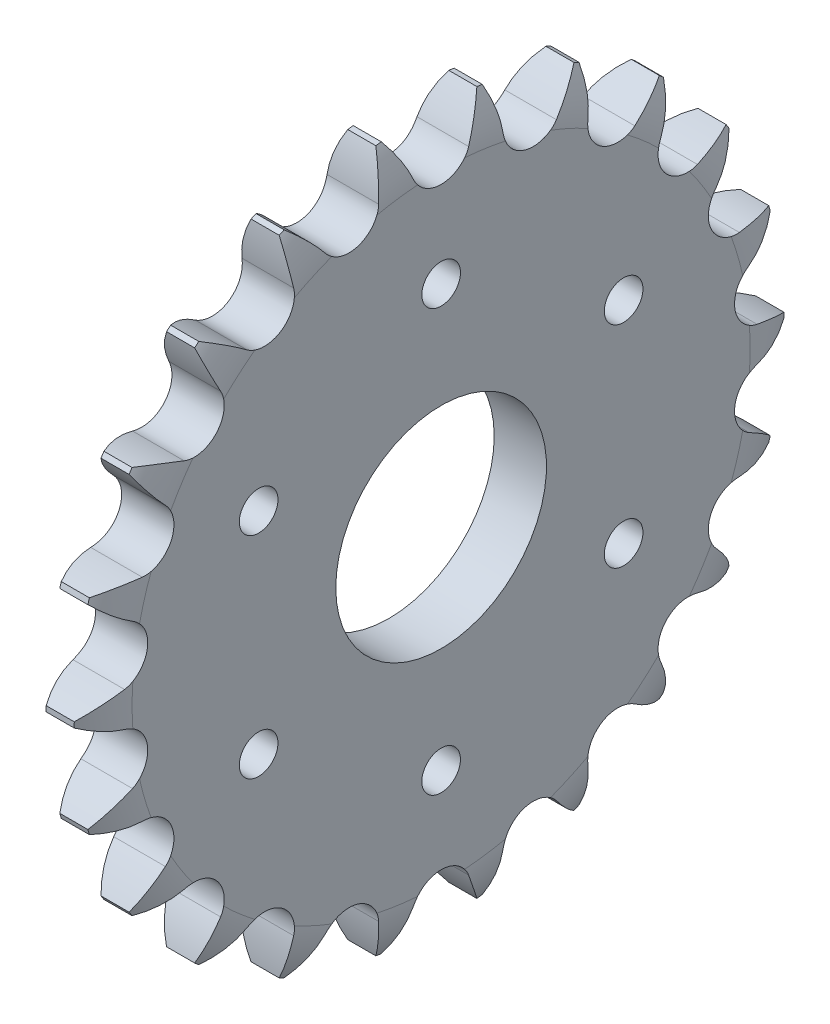
SolidWorks part; units mm, degrees
ref_plane "Plane1" through (0, 0, 0) normal (0, 0, 1) x (1, 0, 0)
ref_plane "Plane2" through (0, 0, 0) normal (0, 1, 0) x (1, 0, 0)
ref_plane "Plane3" through (0, 0, 0) normal (1, 0, 0) x (0, 0, -1)
sketch "Clipboard" plane through (0, 0, 0) normal (0, 1, 0) x (1, 0, 0)
  line L0 (0, 0) -> (14.719, -5.9469)
  line L1 (-15, 0) -> (100, 0) construction
  line L2 (0, 0) -> (-1.3675, 1.5456)
  line L3 (0, 0) -> (-14.8288, 5.6677)
  line L4 (0, 0) -> (2.8743, 1.1613)
  line L5 (0, 0) -> (-46.8476, -17.4728)
  line L6 (0, 0) -> (-7.4026, -4.9946)
  line L7 (-1.3675, 1.5456) -> (44.6582, 21.0824)
  line L8 (-76.2, 38.1) -> (-72.9, 38.1)
  line L9 (-73.5462, 42.5082) -> (-72.9534, 42.6013)
  line L10 (-74, 16.6356) -> (-55.89, 16.6356)
  circle A0 centre (0, 0) radius 5.08
  circle A1 centre (0, 0) radius 37.5
  circle A2 centre (0, 0) radius 37.5
  dimension "Num_teeth" = 22
  dimension "Thickness" = 8.93
sketch "BasProSke" plane through (0, 0, 0) normal (0, 1, 0) x (1, 0, 0)
  line L0 (-10, 0) -> (60, 0) construction
  line L1 (0, 0) -> (0, 52.7889)
  line L2 (0, 0) -> (8.93, 0)
  line L3 (8.93, 0) -> (8.93, 52.7889)
  line L4 (6.8663, 60.6161) -> (2.0638, 60.6161)
  arc A0 (0, 52.7889) -> (2.0638, 60.6161) centre (15.875, 52.7889) cw
  arc A1 (8.93, 52.7889) -> (6.8663, 60.6161) centre (-6.945, 52.7889) ccw
  dimension "D1" = 15.875
  dimension "Thickness" = 8.93
  dimension "Diameter" = 121.2322
revolve "Base-Revolve" add sketch "BasProSke" angle 360 about L0
sketch "TooCutSke" plane through (0, 0, 0) normal (1, 0, 0) x (0, 0, -1)
  line L0 (0, 55.825) -> (4.7557, 53.8992) construction
  line L1 (0, 0) -> (0, 107) construction
  line L2 (0, 55.825) -> (-10, 55.825) construction
  line L3 (0, 55.825) -> (-4.7557, 53.8992) construction
  arc A0 (4.7557, 53.8992) -> (8.5049, 60.5214) centre (31.8771, 42.9164) cw
  arc A1 (4.7557, 53.8992) -> (-4.7557, 53.8992) centre (0, 55.825) cw
  arc A2 (-4.7557, 53.8992) -> (-8.5049, 60.5214) centre (-31.8771, 42.9164) ccw
  arc A3 (8.5049, 60.5214) -> (-8.5049, 60.5214) centre (0, 0) ccw
extrude "ToothCut" cut sketch "TooCutSke" along normal through all
pattern_circular "TeethCuts" count 22 every 16.364 about axis through (-10, 0, 0) along (1, 0, 0) of "ToothCut"
sketch "HubNeaOneSke" plane through (0, 0, 0) normal (-1, 0, 0) x (0, 0, 1)
  circle A0 centre (0, 0) radius 37.5
  dimension "Diameter" = 75
extrude "HubNearOne" [suppressed] add sketch "HubNeaOneSke" along normal blind 41.0705
fillet "HubNearOneFillet" [suppressed] radius 0.6
sketch "HubNeaBotSke" plane through (0, 0, 0) normal (-1, 0, 0) x (0, 0, 1)
  circle A0 centre (0, 0) radius 37.5
  dimension "Diameter" = 75
extrude "HubNearBoth" [suppressed] add sketch "HubNeaBotSke" along normal blind 20.5353
fillet "HubNearBothFillet" [suppressed] radius 0.6
ref_plane "FarPln" through (8.93, 0, 0) normal (1, 0, 0) x (0, 0, -1)
sketch "HubFarSke" plane through (8.93, 0, 0) normal (1, 0, 0) x (0, 0, -1)
  circle A0 centre (0, 0) radius 37.5
  dimension "Diameter" = 75
extrude "HubFar" [suppressed] add sketch "HubFarSke" along normal blind 20.5353
fillet "HubFarFillet" [suppressed] radius 0.6
sketch "BorSke" plane through (0, 0, 0) normal (1, 0, 0) x (0, 0, -1)
  circle A0 centre (0, 0) radius 18
  dimension "Diameter" = 36
extrude "Bore" cut sketch "BorSke" along normal mid plane 100.001
sketch "KeySke" plane through (0, 0, 0) normal (1, 0, 0) x (0, 0, -1)
  line L0 (-5, 0) -> (-5, 21.3)
  line L1 (-5, 21.3) -> (5, 21.3)
  line L2 (5, 21.3) -> (5, 0)
  line L3 (0, 0) -> (0, 34) construction
  line L4 (-5, 0) -> (5, 0)
  dimension "Width" = 10
extrude "Keyway" [suppressed] cut sketch "KeySke" along normal mid plane 100.001
pattern_circular "Keyway2" [suppressed] count 2 every 90 about axis through (-10, 0, 0) along (1, 0, 0) reverse direction yes
ref_axis "Assi1" through (8.93, 0, 0) along (-1, 0, 0)
hole_wizard "Foro per Vite M6-1" positions "Schizzo2" profile "Schizzo3" hole size "M6" standard "ISO"
sketch "Schizzo2" plane through (8.93, 0, 0) normal (1, 0, 0) x (0, 0, -1)
  point P0 (0, 36)
  dimension "D1" = 36
sketch "Schizzo3" plane through (8.93, 36, 0) normal (0, 1, 0) x (0, 0, -1)
  line L0 (0, 0) -> (0, 12)
  line L1 (0, 12) -> (3.3, 10.0172)
  line L2 (3.3, 10.0172) -> (3.3, 0)
  line L5 (3.3, 0) -> (0, 0)
  line L10 (0, 12) -> (-3.3, 10.0172) construction
  line L11 (0, -6.35) -> (0, 107.95) construction
  dimension "Hole Dia." = 6.6
  dimension "Hole Depth" = 12
  dimension "Drill Angle" = 118
pattern_circular "RipetizioneCircolare1" count 6 over 360 about axis through (8.93, 0, 0) along (1, 0, 0) of "Foro per Vite M6-1"
ref_plane "Piano1" through (4.465, 0, 0) normal (1, 0, 0) x (0, 0, -1)
sketch "Schizzo4" plane through (4.465, 0, 0) normal (1, 0, 0) x (0, 0, -1)
  circle A0 centre (0, 0) radius 55.83
  dimension "D1" = 111.66
equation "' \"Pitch@Clipboard\" = 12.7"
equation "' \"Num_strands@Clipboard\" = 1"
equation "' \"Num_teeth@Clipboard\" = 9"
equation "' \"Hub_dia@Clipboard\" = 50"
equation "' \"Overall_len@Clipboard\" = 3"
equation "' \"Diameter@BorSke\" = 12"
equation "' \"T_dim@Clipboard\" = 1"
equation "' \"Width@KeySke\" = 2"
equation "' \"Dr@Clipboard\" = 8.51"
equation "' \"Face_width@Clipboard\" = 7.2"
equation "' \"Side_radius@Clipboard\" = 12.7"
equation "' \"Side_relief@Clipboard\" = 1.27"
equation "' \"Transv_pitch@Clipboard\" = 13.92"
equation "' \"Show_teeth@Clipboard\" = 9"
equation "' \"Fillet_rad@Clipboard\" = 0.6"
equation "' \"Plate_wid@Clipboard\" = 11.8"
equation "\"Num_teeth@Clipboard\" = int( \"Num_teeth@Clipboard\" )"
equation "\"Num_teeth@Clipboard\" = ((sgn( \"Num_teeth@Clipboard\" - 5.0)+1)*( \"Num_teeth@Clipboard\" - 5.0))/2 +5.0"
equation "\"Num_teeth@Clipboard\" = ((sgn( \"Num_teeth@Clipboard\" - 200.0)-1)*( \"Num_teeth@Clipboard\" - 200.0))/-2 +200.0"
equation "\"MHD@Clipboard\" = \"Pitch@Clipboard\" * (1.0 / tan(3.14159265 / \"Num_teeth@Clipboard\" )) - 1.04 * \"Plate_wid@Clipboard\" - 0.76"
equation "\"Thickness@Clipboard\"  = \"Face_width@Clipboard\" + (\"Num_strands@Clipboard\" - 1) * \"Transv_pitch@Clipboard\""
equation "\"OAL@Clipboard\" = \"Thickness@Clipboard\" + 2 * \"Fillet_rad@Clipboard\" + 1"
equation "\"MHD@Clipboard\" = ((sgn( \"MHD@Clipboard\" - \"Hub_dia@Clipboard\" )-1)*( \"MHD@Clipboard\" - \"Hub_dia@Clipboard\" ))/-2+ \"Hub_dia@Clipboard\""
equation "\"OAL@Clipboard\" = ((sgn( \"OAL@Clipboard\" - \"Overall_len@Clipboard\" )+1)*( \"OAL@Clipboard\" - \"Overall_len@Clipboard\" ))/2 + \"Overall_len@Clipboard\" + 0.0005"
equation "\"Num_teeth@TeethCuts\" = int( \"Show_teeth@Clipboard\" ) + 1"
equation "\"Num_teeth@TeethCuts\" = ((sgn( \"Num_teeth@TeethCuts\" - \"Num_teeth@Clipboard\" )-1)*( \"Num_teeth@TeethCuts\" - \"Num_teeth@Clipboard\" ))/-2+ \"Num_teeth@Clipboard\""
equation "\"Num_teeth@TeethCuts\" = ((sgn( \"Num_teeth@TeethCuts\" - 2.0)+1)*( \"Num_teeth@TeethCuts\" - 2.0))/2 +2.0"
equation "\"Angle@TeethCuts\" = 360.0 / \"Num_teeth@Clipboard\""
equation "\"Seat_radius@TooCutSke\" = ( \"Pitch@Clipboard\" / 2.0) / sin(3.14159265 / \"Num_teeth@Clipboard\" ) - \"Dr@Clipboard\" / 2.0 + \"Dr@Clipboard\" * 0.505"
equation "\"R1@TooCutSke\"  = \"Dr@Clipboard\" * 0.505"
equation "\"X@TooCutSke\" = 140.0 - (90.0 / \"Num_teeth@Clipboard\")"
equation "\"R2@TooCutSke\" = 0.12 * \"Dr@Clipboard\" * ( \"Num_teeth@Clipboard\" + 2.0)"
equation "\"Overcut@TooCutSke\" = 0.5 + 0.625 * \"Pitch@Clipboard\" - 0.5 * \"Dr@Clipboard\"  +  \"Pitch@Clipboard\" / 2.0 / sin(3.14159265 / \"Num_teeth@Clipboard\" )"
equation "\"Diameter@BasProSke\" = 2.0 * ( 0.625 * \"Pitch@Clipboard\" - 0.5 * \"Dr@Clipboard\"  +  \"Pitch@Clipboard\" / 2.0 / sin(3.14159265 / \"Num_teeth@Clipboard\" ))"
equation "\"Thickness@BasProSke\"  = \"Thickness@Clipboard\""
equation "\"G1@BasProSke\" =  \"Side_relief@Clipboard\""
equation "\"G2@BasProSke\" =  \"Side_relief@Clipboard\""
equation "\"D1@BasProSke\" =  \"Side_radius@Clipboard\""
equation "\"Diameter@HubNeaOneSke\" = \"MHD@Clipboard\""
equation "\"Length@HubNearOne\" = \"OAL@Clipboard\" - \"Thickness@BasProSke\""
equation "\"Diameter@HubNeaBotSke\" = \"MHD@Clipboard\""
equation "\"Length@HubNearBoth\" = ( \"OAL@Clipboard\" - \"Thickness@BasProSke\" ) / 2.0"
equation "\"D1@HubNearOneFillet\" = \"Fillet_rad@Clipboard\""
equation "\"D1@HubNearBothFillet\" = \"Fillet_rad@Clipboard\""
equation "\"Thickness@FarPln\" = \"Thickness@BasProSke\""
equation "\"Diameter@HubFarSke\" = \"MHD@Clipboard\""
equation "\"Length@HubFar\" = ( \"OAL@Clipboard\" - \"Thickness@BasProSke\" ) / 2.0"
equation "\"D1@HubFarFillet\" = \"Fillet_rad@Clipboard\""
equation "\"D1@Bore\" = \"OAL@Clipboard\" * 2.0"
equation "\"D1@Keyway\" = \"OAL@Clipboard\" * 2.0"
equation "\"Offset@KeySke\" = \"T_dim@Clipboard\" + \"Diameter@BorSke\" / 2.0"
